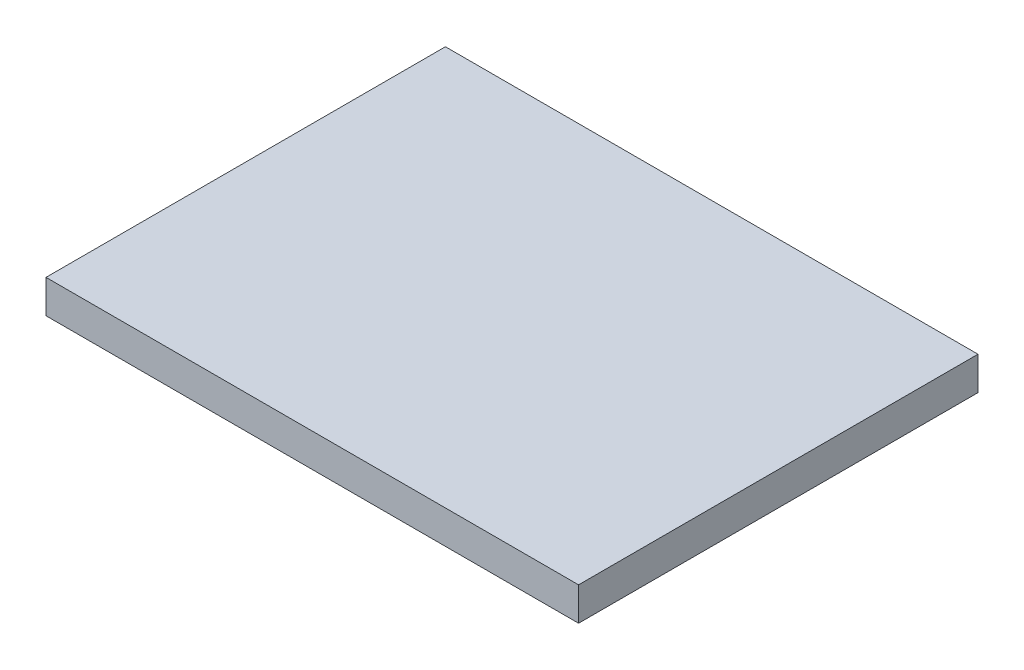
SolidWorks part; units mm, degrees
ref_plane "Front Plane" through (0, 0, 0) normal (0, 0, 1) x (1, 0, 0)
ref_plane "Top Plane" through (0, 0, 0) normal (0, 1, 0) x (1, 0, 0)
ref_plane "Right Plane" through (0, 0, 0) normal (1, 0, 0) x (0, 0, -1)
sketch "Sketch1" plane through (0, 0, 0) normal (0, 1, 0) x (1, 0, 0)
  line L1 (0, 0) -> (80, 0)
  line L3 (0, -60) -> (80, -60)
  line L5 (0, 0) -> (0, -60)
  line L9 (80, 0) -> (80, -60)
  point P1 (9.3019, -19.9891)
  point P3 (7.1232, -20.2386)
  dimension "D1" = 60
  dimension "D2" = 80
extrude "Boss-Extrude1" add sketch "Sketch1" along normal blind 5
